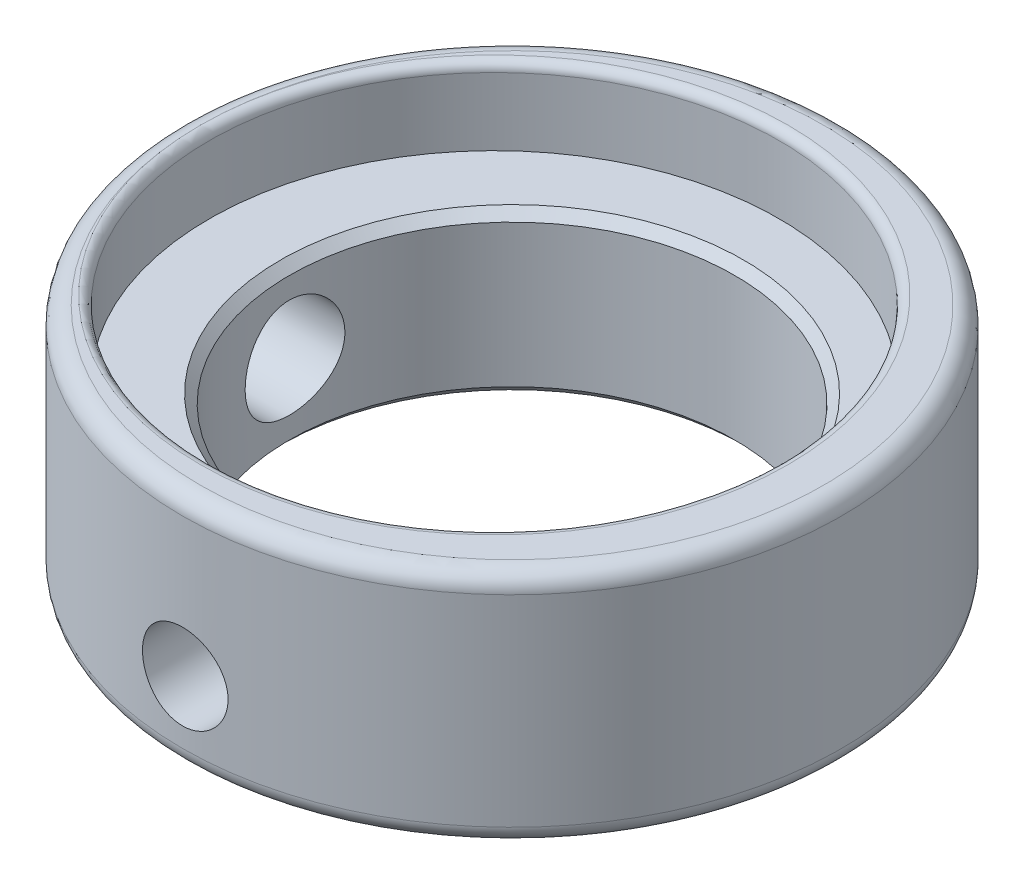
SolidWorks part; units mm, degrees
ref_plane "Спереди" through (0, 0, 0) normal (0, 0, 1) x (1, 0, 0)
ref_plane "Сверху" through (0, 0, 0) normal (0, 1, 0) x (1, 0, 0)
ref_plane "Справа" through (0, 0, 0) normal (1, 0, 0) x (0, 0, -1)
sketch "Эскиз1" plane through (0, 0, 0) normal (0, 1, 0) x (1, 0, 0)
  circle A0 centre (0, 0) radius 12.5
  circle A1 centre (0, 0) radius 18.5
  dimension "D1" = 25
  dimension "D2" = 37
extrude "Бобышка-Вытянуть1" add sketch "Эскиз1" along normal blind 13.3
sketch "Эскиз2" plane through (0, 13.3, 0) normal (0, 1, 0) x (1, 0, 0)
  line L0 (-17, 0) -> (-18.5, 0) construction
  line L1 (15, 0) -> (18.5, 0) construction
  circle A0 centre (-1, 0) radius 16
  circle A1 centre (0, 0) radius 18.5 construction
  dimension "D1" = 3.5
  dimension "D2" = 1.5
extrude "Вырез-Вытянуть1" cut sketch "Эскиз2" against normal blind 4.3
sketch "Эскиз3" plane through (0, 0, 0) normal (1, 0, 0) x (0, 0, -1)
  line L0 (0, 0) -> (0, 9) construction
  line L1 (12.5, 9) -> (-12.5, 9) construction
  circle A0 centre (0, 4.5) radius 2.8
  dimension "D1" = 5.6
extrude "Вырез-Вытянуть2" cut sketch "Эскиз3" against normal through all
fillet "Скругление1" radius 1 2 edges at (0, 0, 18.5) (0, 13.3, 18.5)
fillet "Скругление2" radius 0.5 1 edges at (-1, 13.3, 16)
chamfer "Фаска1" distance 0.5 angle 45 2 edges at (0, 0, 12.5) (0, 9, 12.5)
ref_plane "Плоскость1" through (0, 0, 18.5) normal (0, 0, 1) x (1, 0, 0)
sketch "Эскиз4" plane through (0, 0, 18.5) normal (0, 0, 1) x (1, 0, 0)
  line L0 (0, 0) -> (0, 9) construction
  line L1 (13, 9) -> (-13, 9) construction
  circle A0 centre (0, 4.5) radius 2.4
  dimension "D1" = 4.8
extrude "Вырез-Вытянуть3" cut sketch "Эскиз4" against normal blind 3.6
